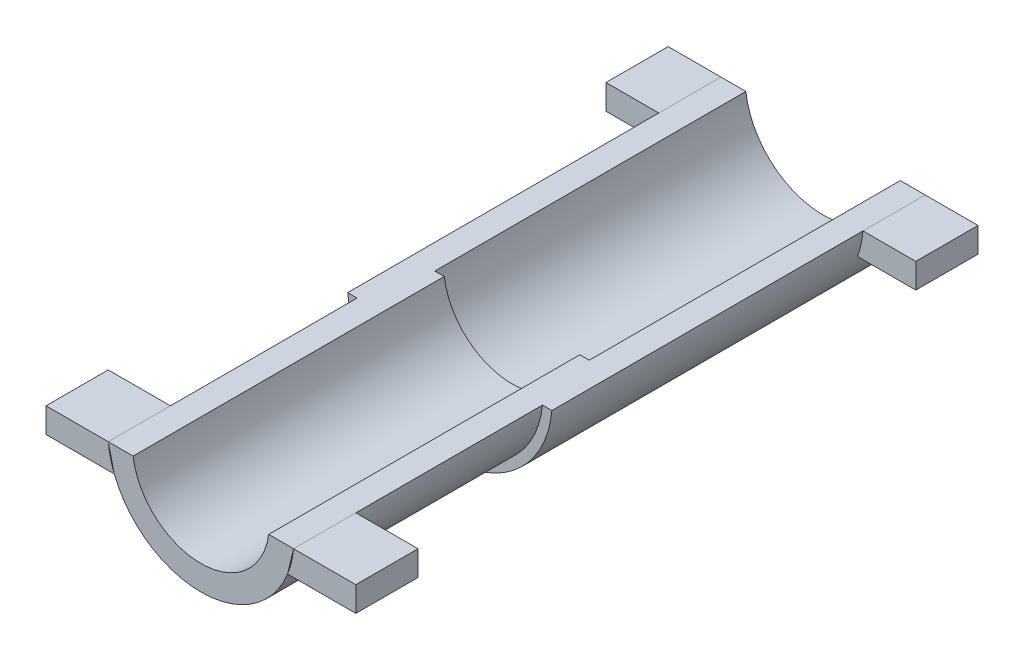
SolidWorks part; units mm, degrees
ref_plane "Front Plane" through (0, 0, 0) normal (0, 0, 1) x (1, 0, 0)
ref_plane "Top Plane" through (0, 0, 0) normal (0, 1, 0) x (1, 0, 0)
ref_plane "Right Plane" through (0, 0, 0) normal (1, 0, 0) x (0, 0, -1)
sketch "Sketch1" plane through (0, 0, 0) normal (0, 0, 1) x (1, 0, 0)
  line L0 (-38.8001, 0) -> (33.896, 0) construction
  line L1 (0, 0) -> (0, -35.9711) construction
  line L2 (-14.8972, -1.5) -> (-10.8972, -1.5)
  line L3 (10.8972, -1.5) -> (14.8972, -1.5)
  arc A0 (-10.8972, -1.5) -> (10.8972, -1.5) centre (0, 0) ccw
  arc A1 (-14.8972, -1.5) -> (14.8972, -1.5) centre (0, 0) ccw
  dimension "D1" = 11
  dimension "D4" = 4
  dimension "D2" = 3
  dimension "D3" = 3
extrude "Boss-Extrude1" add sketch "Sketch1" along normal blind 40
sketch "Sketch2" plane through (0, 0, 40) normal (0, 0, 1) x (1, 0, 0)
  line L0 (14.8972, -1.5) -> (24.8972, -1.5)
  line L1 (24.8972, -1.5) -> (24.8972, -5.5)
  line L2 (24.8972, -5.5) -> (13.9258, -5.5)
  line L3 (13.9258, -5.5) -> (14.8972, -1.5)
  line L4 (14.8972, -1.5) -> (10.8972, -1.5) construction
  line L5 (-14.8972, -1.5) -> (-10.8972, -1.5)
  line L6 (10.8972, -1.5) -> (14.8972, -1.5)
  line L7 (0, 6.9746) -> (0, -27.801) construction
  line L8 (-24.8972, -5.5) -> (-13.9258, -5.5)
  line L9 (-24.8972, -1.5) -> (-24.8972, -5.5)
  line L10 (-14.8972, -1.5) -> (-24.8972, -1.5)
  line L11 (-13.9258, -5.5) -> (-14.8972, -1.5)
  arc A0 (-14.8972, -1.5) -> (14.8972, -1.5) centre (0, 0) ccw
  arc A3 (-14.8972, -1.5) -> (14.8972, -1.5) centre (0, 0) ccw construction
  arc A4 (-10.8972, -1.5) -> (10.8972, -1.5) centre (0, 0) ccw
  arc M10 (10.8972, -1.5) -> (-10.8972, -1.5) centre (0, 0) cw
  line M11 (-10.8972, -1.5) -> (-14.8972, -1.5)
  arc M12 (-14.8972, -1.5) -> (14.8972, -1.5) centre (0, 0) ccw
  line M13 (14.8972, -1.5) -> (10.8972, -1.5)
  dimension "D1" = 10
  dimension "D2" = 4
extrude "Boss-Extrude2" add sketch "Sketch2" along normal blind 10 contours L10 L9 L8 M12 | L7 A4 L11 M11 M12 | L7 A0 L3 M10 M13 | L2 L1 L0 M12 region at (7.9298, -8.9633, 40) region at (19.6993, -3.531, 40) region at (-7.9298, -8.9633, 40) region at (-19.6993, -3.531, 40)
sketch "Sketch3" plane through (0, 0, 0) normal (0, 0, 1) x (1, 0, 0)
  line L0 (-25.166, 0) -> (25.7633, 0) construction
  line L1 (-10.8972, -1.5) -> (-14.8972, -1.5) construction
  line L2 (14.8972, -1.5) -> (10.8972, -1.5) construction
  line L3 (-14.8972, -1.5) -> (-24.8972, -1.5) construction
  line L4 (14.8972, -1.5) -> (24.8972, -1.5) construction
  line L5 (-16.4097, -1.5) -> (-12.4097, -1.5)
  line L6 (12.4097, -1.5) -> (16.4097, -1.5)
  arc A0 (-12.4097, -1.5) -> (12.4097, -1.5) centre (0, 0) ccw
  arc A1 (-16.4097, -1.5) -> (16.4097, -1.5) centre (0, 0) ccw
  dimension "D1" = 12.5
  dimension "D2" = 4
extrude "Boss-Extrude3" add sketch "Sketch3" against normal blind 40 and the other way blind 10
sketch "Sketch5" plane through (0, 0, -40) normal (0, 0, -1) x (-1, 0, 0)
  line L0 (12.4097, -1.5) -> (16.4097, -1.5) construction
  line L1 (14.8972, -1.5) -> (24.8972, -1.5) construction
  line L2 (-16.4097, -1.5) -> (-12.4097, -1.5)
  line L3 (12.4097, -1.5) -> (16.4097, -1.5)
  line L4 (-16.4097, -1.5) -> (-24.8972, -1.5)
  line L5 (-24.8972, -1.5) -> (-24.8972, -5.5)
  line L6 (-24.8972, -5.5) -> (-15.5331, -5.5)
  line L7 (-24.8972, -5.5) -> (-13.9258, -5.5) construction
  line L8 (-15.5331, -5.5) -> (-16.4097, -1.5)
  line L9 (0, 10.4588) -> (0, -22.7884) construction
  line L10 (15.5331, -5.5) -> (16.4097, -1.5)
  line L11 (24.8972, -5.5) -> (15.5331, -5.5)
  line L12 (24.8972, -1.5) -> (24.8972, -5.5)
  line L13 (16.4097, -1.5) -> (24.8972, -1.5)
  arc A0 (-12.4097, -1.5) -> (12.4097, -1.5) centre (0, 0) ccw
  arc A1 (-16.4097, -1.5) -> (16.4097, -1.5) centre (0, 0) ccw
  arc M10 (12.4097, -1.5) -> (-12.4097, -1.5) centre (0, 0) cw
  line M11 (-12.4097, -1.5) -> (-16.4097, -1.5)
  arc M12 (-16.4097, -1.5) -> (16.4097, -1.5) centre (0, 0) ccw
  line M13 (16.4097, -1.5) -> (12.4097, -1.5)
extrude "Boss-Extrude4" add sketch "Sketch5" along normal blind 10 contours L5 L6 L4 M12 | L9 A0 L8 M11 M12 | L9 A1 L10 M10 M13 | L13 L11 L12 M12 region at (20.4742, -3.533, -40) region at (8.8863, -9.9115, -40) region at (-8.8863, -9.9115, -40) region at (-20.4742, -3.533, -40)
ref_plane "Plane_top_lower_100mm" through (0, -100, 0) normal (0, 1, 0) x (1, 0, 0)
sketch "Sketch7" plane through (0, -100, 0) normal (0, 1, 0) x (1, 0, 0)
  line L0 (-212.9666, 0) -> (1123.3863, 0) construction
  line L1 (940, -482.4091) -> (940, 483.6176) construction
  dimension "D1" = 940
ref_plane "Angled Plane" through (0, 0, 0) normal (0.1058, 0.9944, 0) x (0.9944, -0.1058, 0)
